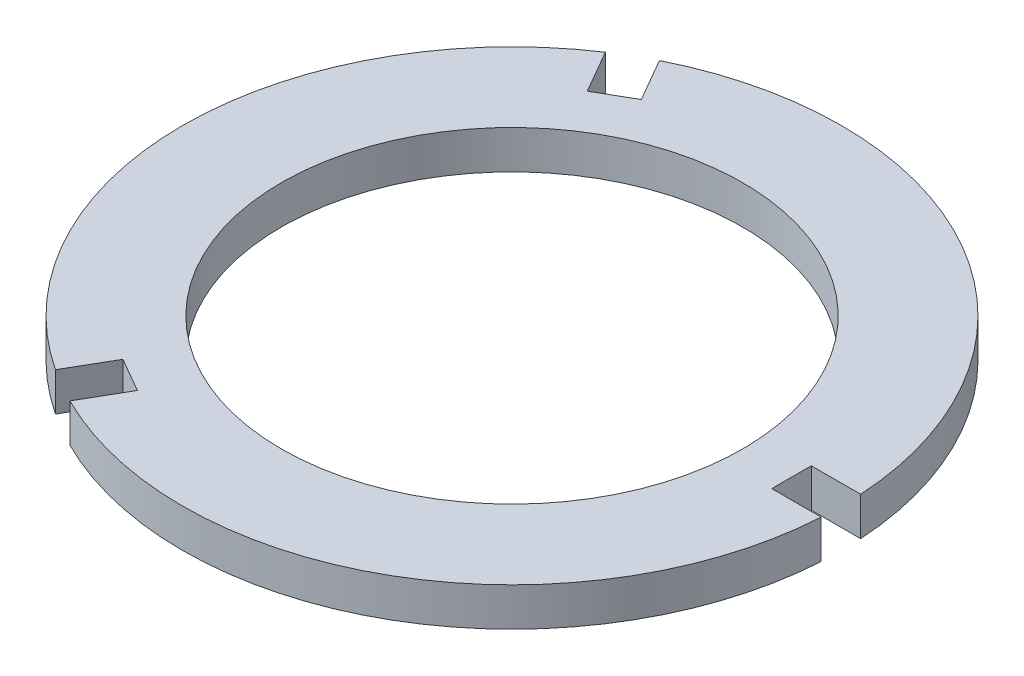
SolidWorks part; units mm, degrees
ref_plane "Alzado" through (0, 0, 0) normal (0, 0, 1) x (1, 0, 0)
ref_plane "Planta" through (0, 0, 0) normal (0, 1, 0) x (1, 0, 0)
ref_plane "Vista lateral" through (0, 0, 0) normal (1, 0, 0) x (0, 0, -1)
sketch "Croquis1" plane through (0, 0, 0) normal (0, 1, 0) x (1, 0, 0)
  circle A1 centre (0, 0) radius 21
  circle A2 centre (0, 0) radius 30
  dimension "D2" = 60
  dimension "D1" = 42
extrude "Saliente-Extruir1" add sketch "Croquis1" along normal blind 3.5
sketch "Croquis2" plane through (0, 0, 0) normal (0, 1, 0) x (1, 0, 0)
  line L0 (0, 0) -> (30, 0) construction
  line L2 (34.55, -1.8) -> (25.45, -1.8)
  line L3 (34.55, -1.8) -> (34.55, 1.8)
  line L4 (34.55, 1.8) -> (25.45, 1.8)
  line L5 (25.45, -1.8) -> (25.45, 1.8)
  line L6 (34.55, -1.8) -> (25.45, 1.8) construction
  line L7 (34.55, 1.8) -> (25.45, -1.8) construction
  circle A1 centre (0, 0) radius 30 construction
  dimension "D1" = 3.6
  dimension "D2" = 9.1
  dimension "D3" = 30
extrude "Cortar-Extruir2" cut sketch "Croquis2" along normal up to next
ref_axis "Eje1" through (0, -0.3, 0) along (0, 1, 0)
pattern_circular "MatrizC1" count 3 over 360 about axis through (0, -0.3, 0) along (0, 1, 0) of "Cortar-Extruir2"
equation "\"dface\"=60"
equation "\"joind\"=9"
equation "\"thickness\"=3.5"
equation "\"D1@Croquis2\"=\"thickness\"+\"clear\""
equation "\"D2@Croquis2\"=\"joind\"+\"clear\""
equation "\"D1@Saliente-Extruir1\"=\"thickness\""
equation "\"D2@Croquis1\"=\"dface\" "
equation "\"clear\"=.1"
equation "\"P\"=.4"
equation "\"D1@Croquis1\"=( \"dface\" ) - 2 * \"joind\""
